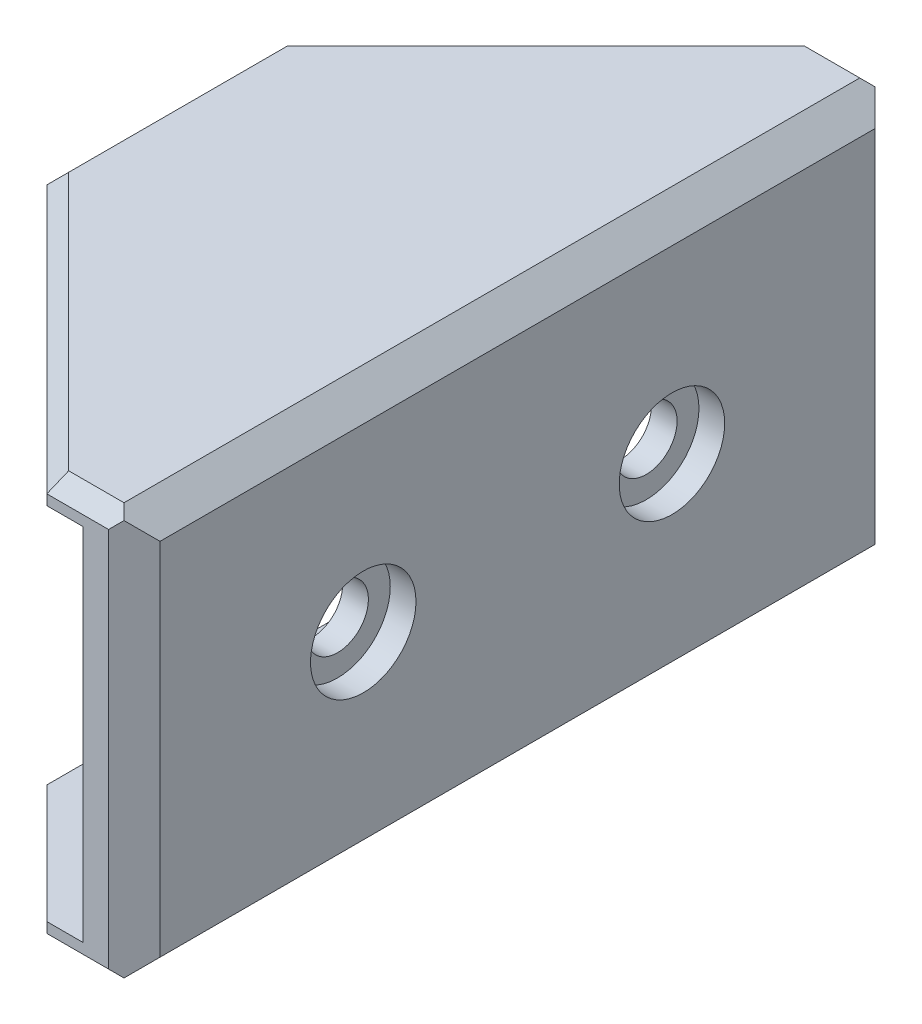
SolidWorks part; units mm, degrees
ref_plane "前视基准面" through (0, 0, 0) normal (0, 0, 1) x (1, 0, 0)
ref_plane "上视基准面" through (0, 0, 0) normal (0, 1, 0) x (1, 0, 0)
ref_plane "右视基准面" through (0, 0, 0) normal (1, 0, 0) x (0, 0, -1)
sketch "草图1" plane through (0, 0, 0) normal (0, 1, 0) x (1, 0, 0)
  line L0 (0, 0) -> (0, 29.8)
  line L1 (0, 29.8) -> (-10.4, 19.4)
  line L2 (-10.4, 19.4) -> (-10.4, 10.4)
  line L3 (-10.4, 10.4) -> (0, 0)
  line L4 (0, 29.8) -> (3.4, 29.8)
  line L5 (3.4, 29.8) -> (3.4, 0)
  line L6 (3.4, 0) -> (0, 0)
  line L7 (1.4, 29.8) -> (1.4, 0)
  dimension "D1" = 45
  dimension "D2" = 45
  dimension "D3" = 3.4
  dimension "D4" = 29.8
  dimension "D5" = 10.4
  dimension "D6" = 2
extrude "凸台-拉伸1" add sketch "草图1" along normal blind 16 contours L6 L5 L4 L0 | L2 L3 L0 L1 | L4 L7 L6 L5 region at (-4.2708, 0, -14.9) region at (0.7, 0, -14.9) region at (2.4, 0, -14.9)
extrude "切除-拉伸1" cut sketch "草图1<3>" along normal blind 14 from offset 1 contours L2 L3 L0 L1 | L7 L4 L0 L6 region at (-4.2708, 0, -14.9) region at (0.7, 0, -14.9)
sketch "草图1<3>" plane through (0, 0, 0) normal (0, 1, 0) x (1, 0, 0) same geometry as "草图1"
sketch "草图4" plane through (-10.4, 0, 0) normal (-1, 0, 0) x (0, 0, 1)
  line L0 (-19.4, 1) -> (-10.4, 1) construction
  line L1 (-33.1252, 1) -> (2.016, 1)
  line L2 (-33.1252, 1) -> (-33.1252, -1.3288)
  line L3 (-33.1252, -1.3288) -> (2.016, -1.3288)
  line L4 (2.016, 1) -> (2.016, -1.3288)
extrude "切除-拉伸4" cut sketch "草图4" against normal blind 5.8
chamfer "倒角2" distance 1 angle 45 4 edges at (3.4, 8, -29.8) (3.4, 8, 0) (3.4, 16, -14.9) (3.4, 0, -14.9)
chamfer "倒角1" distance 0.6 angle 45 10 edges at (1.2, 0, -29.8) (1.2, 0, 0) (-2.3, 0, -2.3) (-2.3, 0, -27.5) (1.2, 16, -29.8) (1.2, 16, 0) (-5.2, 16, -24.6) (-5.2, 16, -5.2) (-10.4, 16, -14.9) (-4.6, 0, -14.9)
sketch "草图2" plane through (3.4, 0, 0) normal (1, 0, 0) x (0, 0, -1)
  line L0 (1, 8) -> (28.8, 8) construction
  line L3 (28.8, 1) -> (28.8, 15) construction
  line L4 (1, 15) -> (1, 1) construction
  line L5 (28.8, 1) -> (28.8, 15) construction
  line L6 (1, 15) -> (1, 1) construction
  circle A0 centre (8.9, 8) radius 1.2
  circle A1 centre (20.9, 8) radius 1.2
  point P10 (14.9, 8)
  dimension "D1" = 6
  dimension "D3" = 2.4
  dimension "D4" = 2.4
  dimension "D2" = 6
extrude "切除-拉伸2" cut sketch "草图2" against normal up to next
sketch "草图3" plane through (3.4, 0, 0) normal (1, 0, 0) x (0, 0, -1)
  circle A0 centre (8.9, 8) radius 2.05
  circle A1 centre (20.9, 8) radius 2.05
  dimension "D1" = 4.1
  dimension "D2" = 4.1
extrude "切除-拉伸3" cut sketch "草图3" against normal blind 1
